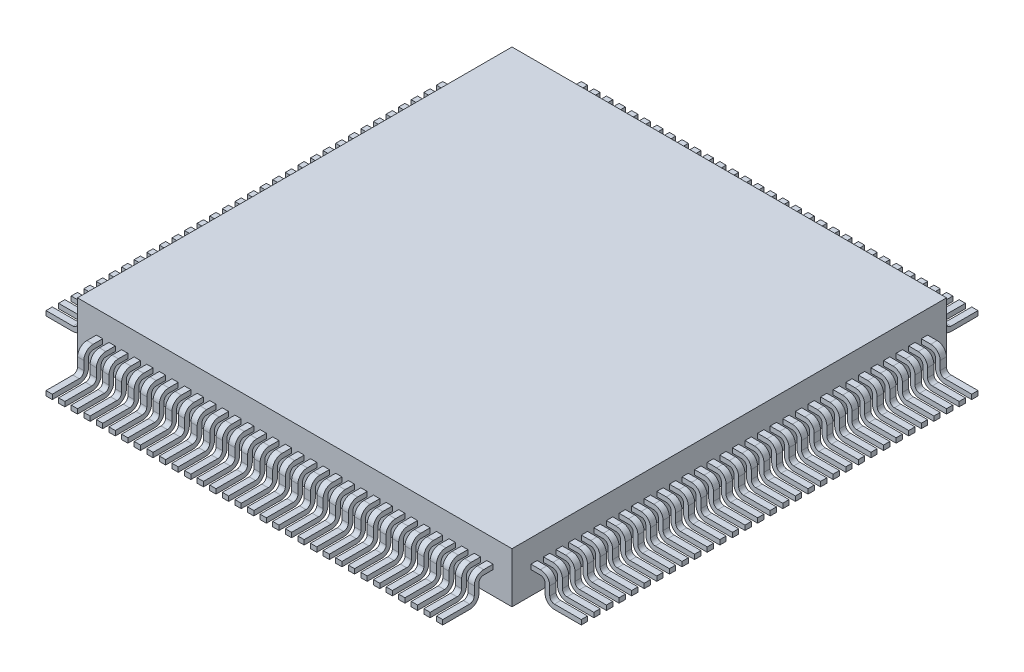
SolidWorks part; units mm, degrees
ref_plane "Front Plane" through (0, 0, 0) normal (0, 0, 1) x (1, 0, 0)
ref_plane "Top Plane" through (0, 0, 0) normal (0, 1, 0) x (1, 0, 0)
ref_plane "Right Plane" through (0, 0, 0) normal (1, 0, 0) x (0, 0, -1)
sketch "Sketch1" plane through (0, 0, 0) normal (0, 1, 0) x (1, 0, 0)
  line L1 (0, 0) -> (13.8, 0)
  line L2 (0, 0) -> (0, 13.8)
  line L3 (0, 13.8) -> (13.8, 13.8)
  line L4 (13.8, 0) -> (13.8, 13.8)
extrude "Boss-Extrude1" add sketch "Sketch1" along normal blind 1.6
ref_plane "Plane1" through (6.9, 0, -6.9) normal (-0.7071, 0, 0.7071) x (0.7071, 0, 0.7071)
ref_plane "Plane2" through (0, 0, 0) normal (0.7071, 0, 0.7071) x (0.7071, 0, -0.7071)
ref_axis "center" through (6.9, 2.586, -6.9) along (0, -1, 0)
sketch "Sketch2" plane through (0, 0, 0) normal (0, 0, 1) x (1, 0, 0)
  line L0 (0.6, 0.8) -> (0, 0.8) construction
  line L1 (0.6, 0.875) -> (0.8, 0.875)
  line L2 (0.6, 0.875) -> (0.6, 0.725)
  line L3 (0.6, 0.725) -> (0.8, 0.725)
  line L4 (0.8, 0.875) -> (0.8, 0.725)
  line L5 (0, 1.6) -> (0, 0) construction
  line L6 (1, 0.875) -> (1.2, 0.875)
  line L7 (0.7, 0.875) -> (0.7, 1.6) construction
  line L8 (0, 1.6) -> (13.8, 1.6) construction
  line L9 (1, 0.875) -> (1, 0.725)
  line L10 (0.7, 0.725) -> (0.7, 0) construction
  line L11 (0, 0) -> (13.8, 0) construction
  line L12 (1, 0.725) -> (1.2, 0.725)
  line L13 (1.2, 0.875) -> (1.2, 0.725)
  line L14 (1.4, 0.875) -> (1.6, 0.875)
  line L15 (1.4, 0.875) -> (1.4, 0.725)
  line L16 (1.4, 0.725) -> (1.6, 0.725)
  line L17 (1.6, 0.875) -> (1.6, 0.725)
  line L18 (1.8, 0.875) -> (2, 0.875)
  line L19 (1.8, 0.875) -> (1.8, 0.725)
  line L20 (1.8, 0.725) -> (2, 0.725)
  line L21 (2, 0.875) -> (2, 0.725)
  line L22 (2.2, 0.875) -> (2.4, 0.875)
  line L23 (2.2, 0.875) -> (2.2, 0.725)
  line L24 (2.2, 0.725) -> (2.4, 0.725)
  line L25 (2.4, 0.875) -> (2.4, 0.725)
  line L26 (2.6, 0.875) -> (2.8, 0.875)
  line L27 (2.6, 0.875) -> (2.6, 0.725)
  line L28 (2.6, 0.725) -> (2.8, 0.725)
  line L29 (2.8, 0.875) -> (2.8, 0.725)
  line L30 (3, 0.875) -> (3.2, 0.875)
  line L31 (3, 0.875) -> (3, 0.725)
  line L32 (3, 0.725) -> (3.2, 0.725)
  line L33 (3.2, 0.875) -> (3.2, 0.725)
  line L34 (3.4, 0.875) -> (3.6, 0.875)
  line L35 (3.4, 0.875) -> (3.4, 0.725)
  line L36 (3.4, 0.725) -> (3.6, 0.725)
  line L37 (3.6, 0.875) -> (3.6, 0.725)
  line L38 (3.8, 0.875) -> (4, 0.875)
  line L39 (3.8, 0.875) -> (3.8, 0.725)
  line L40 (3.8, 0.725) -> (4, 0.725)
  line L41 (4, 0.875) -> (4, 0.725)
  line L42 (4.2, 0.875) -> (4.4, 0.875)
  line L43 (4.2, 0.875) -> (4.2, 0.725)
  line L44 (4.2, 0.725) -> (4.4, 0.725)
  line L45 (4.4, 0.875) -> (4.4, 0.725)
  line L46 (4.6, 0.875) -> (4.8, 0.875)
  line L47 (4.6, 0.875) -> (4.6, 0.725)
  line L48 (4.6, 0.725) -> (4.8, 0.725)
  line L49 (4.8, 0.875) -> (4.8, 0.725)
  line L50 (5, 0.875) -> (5.2, 0.875)
  line L51 (5, 0.875) -> (5, 0.725)
  line L52 (5, 0.725) -> (5.2, 0.725)
  line L53 (5.2, 0.875) -> (5.2, 0.725)
  line L54 (5.4, 0.875) -> (5.6, 0.875)
  line L55 (5.4, 0.875) -> (5.4, 0.725)
  line L56 (5.4, 0.725) -> (5.6, 0.725)
  line L57 (5.6, 0.875) -> (5.6, 0.725)
  line L58 (5.8, 0.875) -> (6, 0.875)
  line L59 (5.8, 0.875) -> (5.8, 0.725)
  line L60 (5.8, 0.725) -> (6, 0.725)
  line L61 (6, 0.875) -> (6, 0.725)
  line L62 (6.2, 0.875) -> (6.4, 0.875)
  line L63 (6.2, 0.875) -> (6.2, 0.725)
  line L64 (6.2, 0.725) -> (6.4, 0.725)
  line L65 (6.4, 0.875) -> (6.4, 0.725)
  line L66 (6.6, 0.875) -> (6.8, 0.875)
  line L67 (6.6, 0.875) -> (6.6, 0.725)
  line L68 (6.6, 0.725) -> (6.8, 0.725)
  line L69 (6.8, 0.875) -> (6.8, 0.725)
  line L70 (7, 0.875) -> (7.2, 0.875)
  line L71 (7, 0.875) -> (7, 0.725)
  line L72 (7, 0.725) -> (7.2, 0.725)
  line L73 (7.2, 0.875) -> (7.2, 0.725)
  line L74 (7.4, 0.875) -> (7.6, 0.875)
  line L75 (7.4, 0.875) -> (7.4, 0.725)
  line L76 (7.4, 0.725) -> (7.6, 0.725)
  line L77 (7.6, 0.875) -> (7.6, 0.725)
  line L78 (7.8, 0.875) -> (8, 0.875)
  line L79 (7.8, 0.875) -> (7.8, 0.725)
  line L80 (7.8, 0.725) -> (8, 0.725)
  line L81 (8, 0.875) -> (8, 0.725)
  line L82 (8.2, 0.875) -> (8.4, 0.875)
  line L83 (8.2, 0.875) -> (8.2, 0.725)
  line L84 (8.2, 0.725) -> (8.4, 0.725)
  line L85 (8.4, 0.875) -> (8.4, 0.725)
  line L86 (8.6, 0.875) -> (8.8, 0.875)
  line L87 (8.6, 0.875) -> (8.6, 0.725)
  line L88 (8.6, 0.725) -> (8.8, 0.725)
  line L89 (8.8, 0.875) -> (8.8, 0.725)
  line L90 (9, 0.875) -> (9.2, 0.875)
  line L91 (9, 0.875) -> (9, 0.725)
  line L92 (9, 0.725) -> (9.2, 0.725)
  line L93 (9.2, 0.875) -> (9.2, 0.725)
  line L94 (9.4, 0.875) -> (9.6, 0.875)
  line L95 (9.4, 0.875) -> (9.4, 0.725)
  line L96 (9.4, 0.725) -> (9.6, 0.725)
  line L97 (9.6, 0.875) -> (9.6, 0.725)
  line L98 (9.8, 0.875) -> (10, 0.875)
  line L99 (9.8, 0.875) -> (9.8, 0.725)
  line L100 (9.8, 0.725) -> (10, 0.725)
  line L101 (10, 0.875) -> (10, 0.725)
  line L102 (10.2, 0.875) -> (10.4, 0.875)
  line L103 (10.2, 0.875) -> (10.2, 0.725)
  line L104 (10.2, 0.725) -> (10.4, 0.725)
  line L105 (10.4, 0.875) -> (10.4, 0.725)
  line L106 (10.6, 0.875) -> (10.8, 0.875)
  line L107 (10.6, 0.875) -> (10.6, 0.725)
  line L108 (10.6, 0.725) -> (10.8, 0.725)
  line L109 (10.8, 0.875) -> (10.8, 0.725)
  line L110 (11, 0.875) -> (11.2, 0.875)
  line L111 (11, 0.875) -> (11, 0.725)
  line L112 (11, 0.725) -> (11.2, 0.725)
  line L113 (11.2, 0.875) -> (11.2, 0.725)
  line L114 (11.4, 0.875) -> (11.6, 0.875)
  line L115 (11.4, 0.875) -> (11.4, 0.725)
  line L116 (11.4, 0.725) -> (11.6, 0.725)
  line L117 (11.6, 0.875) -> (11.6, 0.725)
  line L118 (11.8, 0.875) -> (12, 0.875)
  line L119 (11.8, 0.875) -> (11.8, 0.725)
  line L120 (11.8, 0.725) -> (12, 0.725)
  line L121 (12, 0.875) -> (12, 0.725)
  line L122 (12.2, 0.875) -> (12.4, 0.875)
  line L123 (12.2, 0.875) -> (12.2, 0.725)
  line L124 (12.2, 0.725) -> (12.4, 0.725)
  line L125 (12.4, 0.875) -> (12.4, 0.725)
  line L126 (12.6, 0.875) -> (12.8, 0.875)
  line L127 (12.6, 0.875) -> (12.6, 0.725)
  line L128 (12.6, 0.725) -> (12.8, 0.725)
  line L129 (12.8, 0.875) -> (12.8, 0.725)
  line L130 (13, 0.875) -> (13.2, 0.875)
  line L131 (13, 0.875) -> (13, 0.725)
  line L132 (13, 0.725) -> (13.2, 0.725)
  line L133 (13.2, 0.875) -> (13.2, 0.725)
  dimension "D1" = 32
sketch "Sketch3" plane through (0, 0, 0) normal (1, 0, 0) x (0, 0, -1)
  line L0 (0, 0.8) -> (-0.3007, 0.8)
  line L1 (0, 0.875) -> (0, 0.725) construction
  line L2 (-0.5237, 0.577) -> (-0.5237, 0.298)
  line L3 (-0.7467, 0.075) -> (-1.6, 0.075)
  line L4 (-0.3007, 0.577) -> (-0.5237, 0.577) construction
  line L5 (-0.5237, 0.298) -> (-0.7467, 0.298) construction
  line L6 (-0.7467, 0.298) -> (-0.7467, 0.075) construction
  line L7 (-0.3007, 0.577) -> (-0.3007, 0.8) construction
  arc A0 (-0.3007, 0.8) -> (-0.5237, 0.577) centre (-0.3007, 0.577) ccw
  arc A1 (-0.5237, 0.298) -> (-0.7467, 0.075) centre (-0.7467, 0.298) cw
sweep "Sweep1" add profiles "Sketch2" path "Sketch3"
pattern_circular "CirPattern1" count 4 every 90 about axis through (6.9, 2.586, -6.9) along (0, -1, 0) of "Sweep1"
